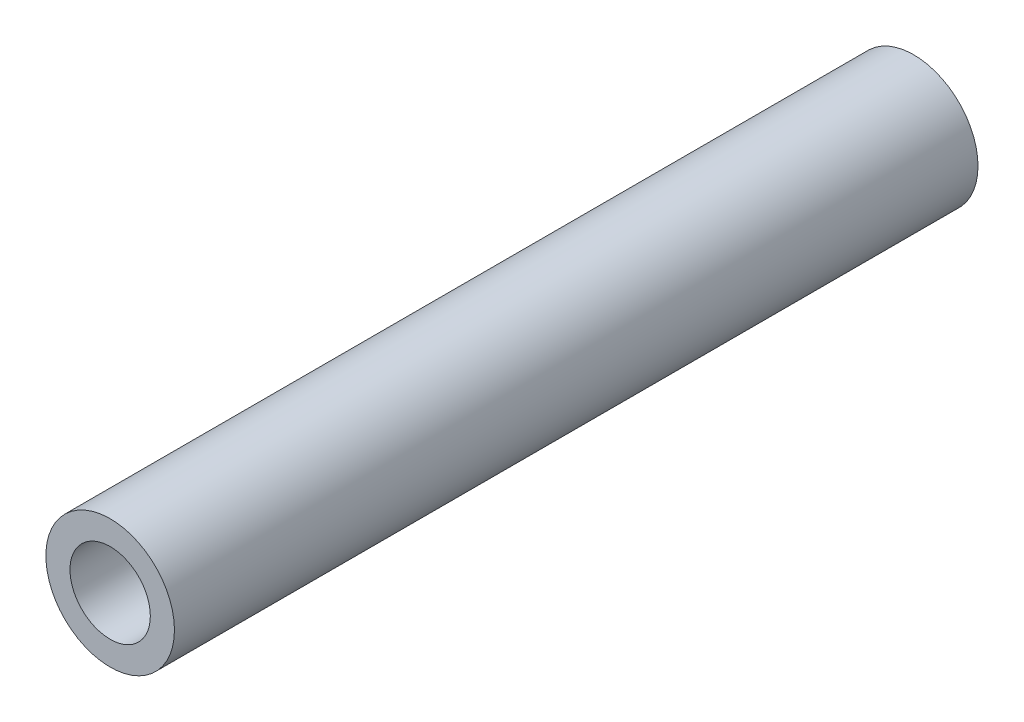
SolidWorks part; units mm, degrees
ref_plane "Front Plane" through (0, 0, 0) normal (0, 0, 1) x (1, 0, 0)
ref_plane "Top Plane" through (0, 0, 0) normal (0, 1, 0) x (1, 0, 0)
ref_plane "Right Plane" through (0, 0, 0) normal (1, 0, 0) x (0, 0, -1)
sketch "Real Length Sketch" plane through (0, 0, 0) normal (1, 0, 0) x (0, 0, -1)
  point P0 (0, 0)
  point P1 (2500, 0)
  dimension "Length" = 2500
sketch "Cross Section Sketch" plane through (0, 0, 0) normal (0, 0, 1) x (1, 0, 0)
  circle A0 centre (0, 0) radius 2
  circle A1 centre (0, 0) radius 1.25
  dimension "OD" = 4
  dimension "ID" = 2.5
extrude "Extrude Length" add sketch "Cross Section Sketch" along normal mid plane 25
